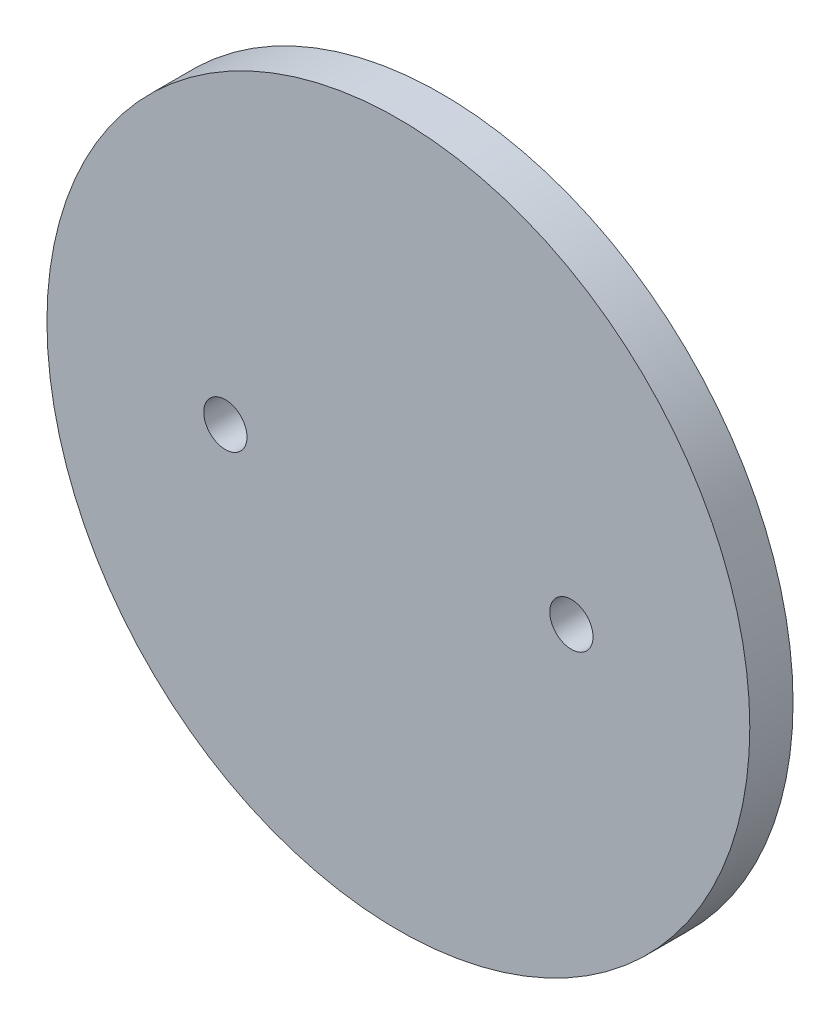
SolidWorks part; units mm, degrees
ref_plane "Front Plane" through (0, 0, 0) normal (0, 0, 1) x (1, 0, 0)
ref_plane "Top Plane" through (0, 0, 0) normal (0, 1, 0) x (1, 0, 0)
ref_plane "Right Plane" through (0, 0, 0) normal (1, 0, 0) x (0, 0, -1)
sketch "Sketch1" plane through (0, 0, 0) normal (0, 0, 1) x (1, 0, 0)
  circle A0 centre (0, 0) radius 20.6375
extrude "Boss-Extrude1" add sketch "Sketch1" along normal blind 2.54
sketch "Sketch2" plane through (0, 0, 2.54) normal (0, 0, 1) x (1, 0, 0)
  line L0 (-20.6375, 0) -> (20.6375, 0)
  circle A0 centre (0, 0) radius 20.6375 construction
  circle A1 centre (-10.16, 0) radius 1.27
  circle A2 centre (10.16, 0) radius 1.27
  point P7 (0, 0)
  dimension "D1" = 10.16
  dimension "D2" = 10.16
extrude "Cut-Extrude1" cut sketch "Sketch2" against normal through all contours L0 A1 | L0 A1 | L0 A2 | L0 A2 region at (-10.16, 0.539, 2.54) region at (10.16, 0.539, 2.54) region at (10.16, -0.539, 2.54) region at (-10.16, -0.539, 2.54)
